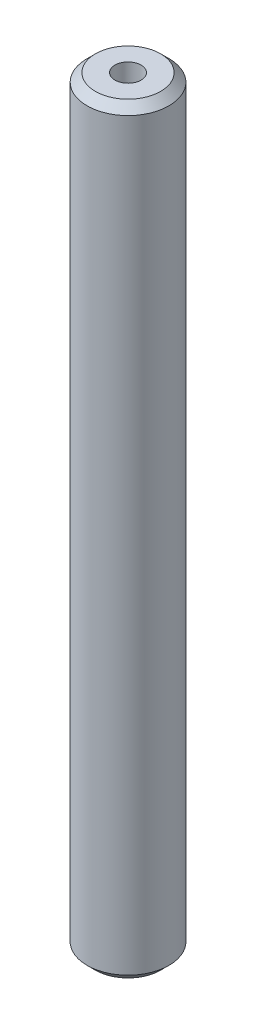
SolidWorks part; units mm, degrees
ref_plane "Front Plane" through (0, 0, 0) normal (0, 0, 1) x (1, 0, 0)
ref_plane "Top Plane" through (0, 0, 0) normal (0, 1, 0) x (1, 0, 0)
ref_plane "Right Plane" through (0, 0, 0) normal (1, 0, 0) x (0, 0, -1)
sketch "Sketch1" plane through (0, 0, 0) normal (0, 1, 0) x (1, 0, 0)
  circle A0 centre (0, 0) radius 25
  dimension "SHAFT_OD" = 50
extrude "Boss-Extrude1" add sketch "Sketch1" along normal blind 464.8197
sketch "Sketch2" plane through (0, 0, 0) normal (0, 1, 0) x (1, 0, 0)
  circle A0 centre (0, 0) radius 7.9826
  dimension "BORE_D" = 15.9651
extrude "Cut-Extrude1" cut sketch "Sketch2" along normal through all
chamfer "Chamfer1" distance 5.0803 angle 45 2 edges at (0, 464.8197, 25) (0, 0, 25)
